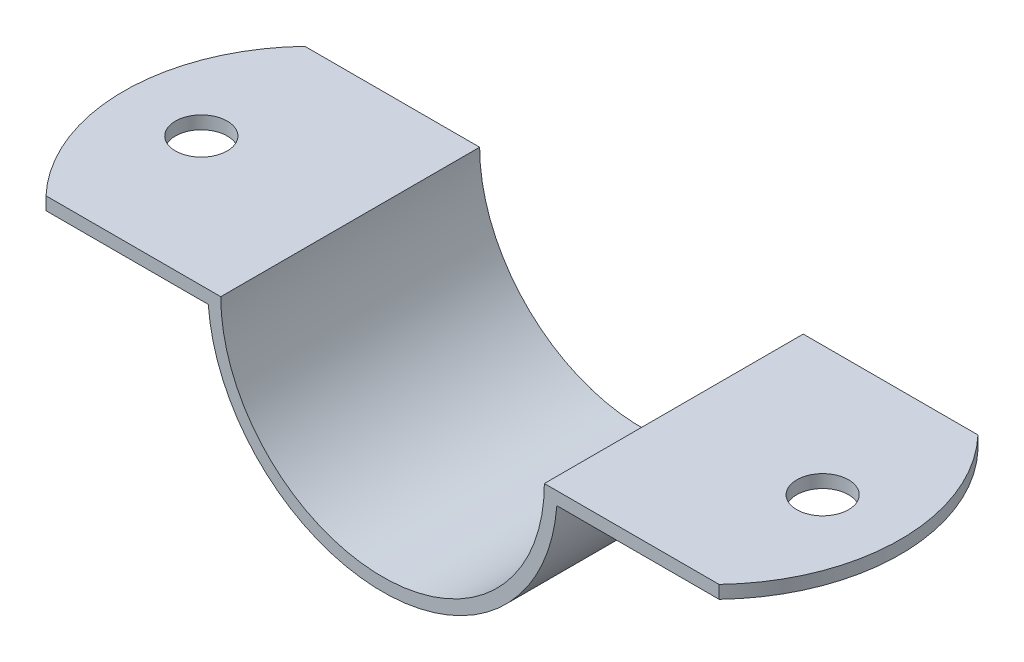
SolidWorks part; units mm, degrees
ref_plane "Front Plane" through (0, 0, 0) normal (0, 0, 1) x (1, 0, 0)
ref_plane "Top Plane" through (0, 0, 0) normal (0, 1, 0) x (1, 0, 0)
ref_plane "Right Plane" through (0, 0, 0) normal (1, 0, 0) x (0, 0, -1)
sketch "Sketch1" plane through (0, 0, 0) normal (0, 0, 1) x (1, 0, 0)
  line L0 (12.5, 0) -> (30, 0)
  line L1 (-12.5, 0) -> (-30, 0)
  line L2 (30, 0) -> (30, -1)
  line L3 (30, -1) -> (13.4629, -1)
  line L5 (-30, 0) -> (-30, -1)
  line L6 (-30, -1) -> (-13.4629, -1)
  arc A0 (12.5, 0) -> (-12.5, 0) centre (0, 0) cw
  arc A1 (-13.4629, -1) -> (13.4629, -1) centre (0, 0) ccw
  dimension "D1" = 17.5
  dimension "D2" = 12.5
  dimension "D4" = 13.5
  dimension "D3" = 17.5
  dimension "D5" = 1
extrude "Boss-Extrude1" add sketch "Sketch1" along normal blind 20
sketch "Sketch2" plane through (0, 0, 0) normal (0, 1, 0) x (1, 0, 0)
  line L0 (0, -25.5999) -> (0, 6.6758)
  line L1 (32.6344, -10) -> (-30.9847, -10) construction
  line L2 (30, 0) -> (12.5, 0) construction
  line L6 (-26, 8.1804) -> (-26, -25.5999) construction
  line L7 (-30, -20) -> (-30, 0) construction
  line L8 (26, 0) -> (26, -29.3785)
  line L9 (30, -20) -> (30, 0) construction
  line L10 (-12.5, -20) -> (-30, -20) construction
  line L11 (-12.5, 0) -> (-30, 0) construction
  line L12 (30, -20) -> (12.5, -20) construction
  line L13 (-26, -20) -> (-30, -20)
  line L14 (-30, -20) -> (-30, 0)
  line L15 (-30, 0) -> (-26, 0)
  line L16 (26, -20) -> (22.5564, -20)
  line L18 (30, 0) -> (26, 0)
  line L19 (-20, 12.2788) -> (-20, -36.1663) construction
  line L20 (20, 11.0269) -> (20, -33.2299) construction
  arc A0 (-26, -20) -> (-26, 0) centre (-15.5, -10) cw
  arc A1 (26, 0) -> (26, -20) centre (15.5, -10) cw
  circle A2 centre (-26, -10) radius 2
  circle A3 centre (20, -10) radius 2
  point P11 (18.2771, 7.377)
  line M9 (30, 0) -> (12.5, 0)
  line M11 (12.5, -20) -> (30, -20)
  line M12 (30, -20) -> (30, 0)
  dimension "D1" = 10
  dimension "D2" = 4
  dimension "D3" = 4
  dimension "D4" = 10
  dimension "D5" = 10
extrude "Cut-Extrude1" cut sketch "Sketch2" against normal blind 20 contours A3 | A1 M12 M11 | A1 M9 M12 | L14 A0 L15 | L13 A0 L14 | A2 region at (28.8349, 0, 2.4258) region at (28.8349, 0, 17.5742) region at (-28.8349, 0, 2.4258) region at (-28.8349, 0, 17.5742) region at (-26, 0, 10) region at (20, 0, 10)
sketch "Sketch3" plane through (0, -1, 0) normal (0, -1, 0) x (1, 0, 0)
  line L0 (24, 24.4098) -> (24, -7.771) construction
  line L1 (-24, -10.8822) -> (-24, 30.8822) construction
  line L2 (20, 10) -> (50020, 10) construction
  line L3 (-30, -4.4098) -> (-30, 24.4098) construction
  line L4 (30, -5.8973) -> (30, 25.8973) construction
  circle A0 centre (24, 10) radius 2
  circle A1 centre (-24, 10) radius 2
  arc A2 (-25, 11.7321) -> (-25, 8.2679) centre (-26, 10) ccw
  circle A3 centre (20, 10) radius 2
  point P3 (20, 10)
  point P9 (-24, 10)
  point P16 (-30, 10)
  point P19 (30, 10)
  circle M6 centre (20, 10) radius 2
  dimension "D1" = 6
  dimension "D2" = 6
extrude "Boss-Extrude3" add sketch "Sketch3" along normal blind 20 separate body contours A1 A2 | M6 region at (20, -1, 10) region at (-26.642, -1, 10)
sketch "Sketch4" plane through (0, -21, 0) normal (0, -1, 0) x (1, 0, 0)
  circle A0 centre (20, 10) radius 2
  circle A1 centre (-24, 10) radius 2
extrude "Cut-Extrude3" cut sketch "Sketch4" against normal blind 20
extrude "Cut-Extrude4" cut sketch "Sketch4<2>" against normal blind 29
sketch "Sketch4<2>" plane through (0, -21, 0) normal (0, -1, 0) x (1, 0, 0) same geometry as "Sketch4"
sketch "Sketch5" plane through (0, -21, 0) normal (0, -1, 0) x (1, 0, 0)
  arc A0 (-25, 11.7321) -> (-25, 8.2679) centre (-26, 10) ccw
  arc A1 (-25, 11.7321) -> (-25, 8.2679) centre (-24, 10) ccw construction
  arc A2 (-25, 11.7321) -> (-25, 8.2679) centre (-26, 10) ccw construction
  arc A3 (-25, 11.7321) -> (-25, 8.2679) centre (-24, 10) ccw
  arc M1 (-25, 8.2679) -> (-25, 11.7321) centre (-24, 10) cw
  arc M2 (-25, 11.7321) -> (-25, 8.2679) centre (-26, 10) ccw
extrude "Cut-Extrude6" cut sketch "Sketch5" against normal blind 20 contours M2 M1 region at (-26.642, -21, 10)
sketch "Sketch6" plane through (0, -1, 0) normal (0, -1, 0) x (1, 0, 0)
  arc A0 (-25, 11.7321) -> (-25, 8.2679) centre (-26, 10) ccw
  arc A1 (-25, 11.7321) -> (-25, 8.2679) centre (-26, 10) ccw construction
  arc A2 (-25, 11.7321) -> (-25, 8.2679) centre (-24, 10) ccw
  arc M5 (-25, 8.2679) -> (-25, 11.7321) centre (-26, 10) cw
extrude "Boss-Extrude4" add sketch "Sketch6" against normal blind 1 contours A2 M5 region at (-26.642, -1, 10)
sketch "Sketch7" plane through (0, -1, 0) normal (0, -1, 0) x (1, 0, 0)
  line L0 (30, 10) -> (30, -6.07) construction
  line L1 (24, -6.07) -> (24, 24.7417) construction
  arc A0 (26, 0) -> (26, 20) centre (15.5, 10) ccw construction
  circle A1 centre (24, 10) radius 2
  circle A2 centre (20, 10) radius 2
  circle M4 centre (20, 10) radius 2
  dimension "D1" = 6
extrude "Boss-Extrude5" add sketch "Sketch7" against normal blind 1 contours M4 region at (20, -1, 10)
sketch "Sketch8" plane through (0, -1, 0) normal (0, -1, 0) x (1, 0, 0)
  line L0 (24, -3.0816) -> (24, 36.1881) construction
  line L1 (30, 10) -> (19.5617, 10) construction
  arc A0 (26, 0) -> (26, 20) centre (15.5, 10) ccw construction
  circle A1 centre (24, 10) radius 2
  point P5 (30, 10)
  dimension "D1" = 6
extrude "Cut-Extrude7" cut sketch "Sketch8" against normal blind 1
